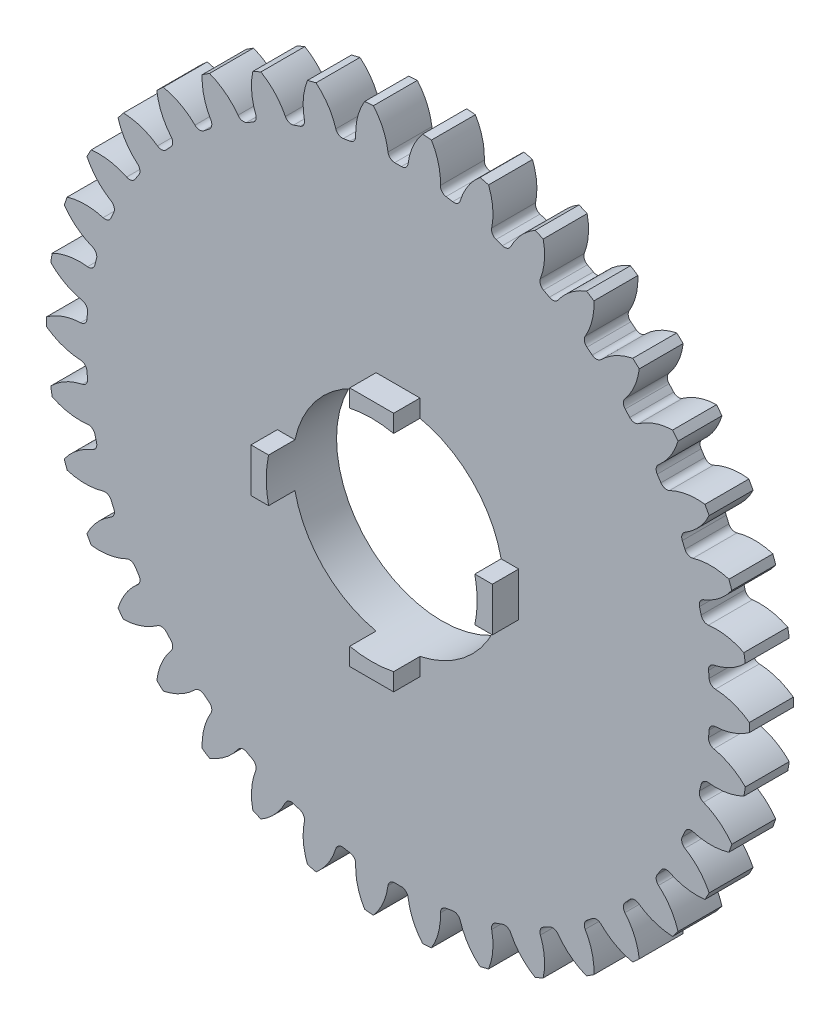
SolidWorks part; units mm, degrees
ref_plane "Front Plane" through (0, 0, 0) normal (0, 0, 1) x (1, 0, 0)
ref_plane "Top Plane" through (0, 0, 0) normal (0, 1, 0) x (1, 0, 0)
ref_plane "Right Plane" through (0, 0, 0) normal (1, 0, 0) x (0, 0, -1)
sketch "Sketch1" plane through (0, 0, 0) normal (0, 0, 1) x (1, 0, 0)
  line L4 (-1.0922, 35.4832) -> (0, 0) construction
  line L5 (0, 0) -> (0, 40) construction
  line L6 (0, 0) -> (3.3032, 39.8634) construction
  line L7 (-1.6208, 37.9654) -> (0.7905, 38.9615) construction
  line L8 (-1.6208, 37.9654) -> (0.4025, 38.0518) construction
  line L11 (1.6208, 37.9654) -> (-1.6208, 37.9654) construction
  circle A0 centre (0, 0) radius 35.5
  circle A1 centre (0, 0) radius 38 construction
  circle A2 centre (0, 0) radius 40
  arc A3 (-2.8046, 39.9016) -> (-1.0922, 35.4832) centre (-8.2141, 35.264) cw
  arc A4 (2.8046, 39.9016) -> (1.0922, 35.4832) centre (8.2141, 35.264) ccw
  point P5 (-38, 0)
  point P6 (-40, 0)
  point P7 (-35.5, 0)
  point P12 (-1.6208, 37.9654)
  point P22 (1.6208, 37.9654)
  dimension "D5" = 76
  dimension "D1" = 2.5
  dimension "D2" = 2
  dimension "D3" = 20
  dimension "D4" = 3.2416
  dimension "D6" = 4.737
  dimension "D7" = 0.5
extrude "Boss-Extrude1" add sketch "Sketch1" against normal blind 5 contours A2
extrude "Cut-Extrude1" cut sketch "Sketch1<4>" against normal blind 10 contours A4 A2 A3 A0 region at (0, 38.1129, 0)
sketch "Sketch1<4>" plane through (0, 0, 0) normal (0, 0, 1) x (1, 0, 0) same geometry as "Sketch1"
fillet "Fillet2" radius 0.76 2 edges at (1.0922, 35.4832, -2.5) (-1.0922, 35.4832, -2.5)
ref_axis "Axis1" through (0, 0, 0) along (0, 0, 1)
pattern_circular "CirPattern2" count 38 over 360 about axis through (0, 0, 0) along (0, 0, 1) of "Cut-Extrude1", "Fillet2"
sketch "Sketch2" plane through (0, 0, 0) normal (0, 0, 1) x (1, 0, 0)
  circle A0 centre (0, 0) radius 12
  dimension "D1" = 24
extrude "Cut-Extrude2" cut sketch "Sketch2" against normal up to surface (5 mm away) up to face at (0, 0, -5)
sketch "Sketch3" plane through (0, 0, 0) normal (0, 0, 1) x (1, 0, 0)
  line L0 (-2.5, 11.7367) -> (-2.5, 13.7367)
  line L1 (-2.5, 13.7367) -> (2.5, 13.7367)
  line L2 (2.5, 13.7367) -> (2.5, 11.7367)
  line L3 (0, 0) -> (0, 12) construction
  line L4 (13.7367, -2.5) -> (11.7367, -2.5)
  line L5 (13.7367, 2.5) -> (13.7367, -2.5)
  line L6 (11.7367, 2.5) -> (13.7367, 2.5)
  line L7 (-2.5, -13.7367) -> (-2.5, -11.7367)
  line L8 (2.5, -13.7367) -> (-2.5, -13.7367)
  line L9 (2.5, -11.7367) -> (2.5, -13.7367)
  line L10 (-13.7367, 2.5) -> (-11.7367, 2.5)
  line L11 (-13.7367, -2.5) -> (-13.7367, 2.5)
  line L12 (-11.7367, -2.5) -> (-13.7367, -2.5)
  circle A0 centre (0, 0) radius 12 construction
  arc A1 (-2.5, 11.7367) -> (2.5, 11.7367) centre (0, 0) cw
  arc A2 (11.7367, 2.5) -> (11.7367, -2.5) centre (0, 0) cw
  arc A3 (2.5, -11.7367) -> (-2.5, -11.7367) centre (0, 0) cw
  arc A4 (-11.7367, -2.5) -> (-11.7367, 2.5) centre (0, 0) cw
  point P24 (0, 0)
  dimension "D4" = 4
  dimension "D1" = 2.5
  dimension "D2" = 2.5
  dimension "D3" = 2
extrude "Boss-Extrude2" add sketch "Sketch3" along normal blind 3
equation "\"backlash\"= 0.1mm"
equation "\"module\"= 2mm"
equation "\"pressureAngle\"= 20deg"
equation "\"width\"= 10mm"
equation "\"D1@Sketch1\"= 1.25 * \"module\""
equation "\"D2@Sketch1\"=\"module\""
equation "\"D5@Sketch1\"=\"module\"*\"numberOfTeeth\""
equation "\"D1@Boss-Extrude1\"=\"width\"-5"
equation "\"D3@Sketch1\"=\"pressureAngle\""
equation "\"D1@Cut-Extrude1\"=\"width\""
equation "\"D1@CirPattern2\"=\"numberOfTeeth\""
equation "\"D1@Fillet2\"=0.38*\"module\""
equation "\"D4@Sketch1\"=pi*\"module\"/2+\"backlash\""
equation "\"numberOfTeeth\"= 38"
equation "\"D6@Sketch1\"=180/\"numberOfTeeth\""
equation "\"toothTipProfile\"= 1mm"
equation "\"D7@Sketch1\"=\"toothTipProfile\"/2"
equation "\"lengthOverallRack\"= pi * \"module\" * \"numberOfTeethRack\""
equation "\"numberOfTeethRack\"= 20"
